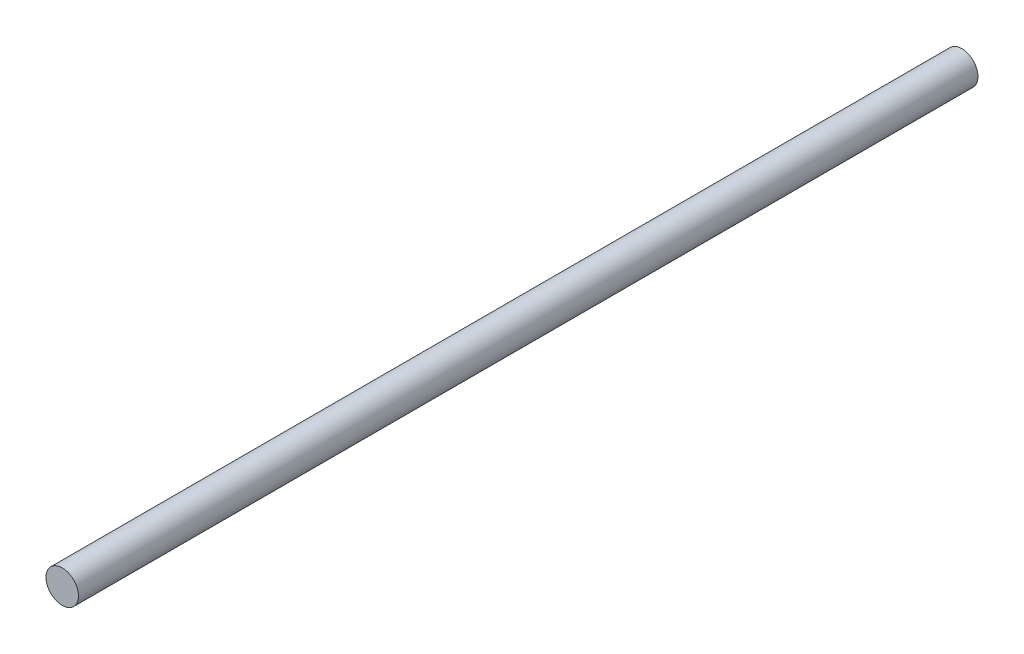
SolidWorks part; units mm, degrees
ref_plane "Спереди" through (0, 0, 0) normal (0, 0, 1) x (1, 0, 0)
ref_plane "Сверху" through (0, 0, 0) normal (0, 1, 0) x (1, 0, 0)
ref_plane "Справа" through (0, 0, 0) normal (1, 0, 0) x (0, 0, -1)
sketch "Эскиз1" plane through (0, 0, 0) normal (0, 0, 1) x (1, 0, 0)
  circle A0 centre (0, 0) radius 6
  dimension "D1" = 12
extrude "Бобышка-Вытянуть1" add sketch "Эскиз1" along normal blind 332
